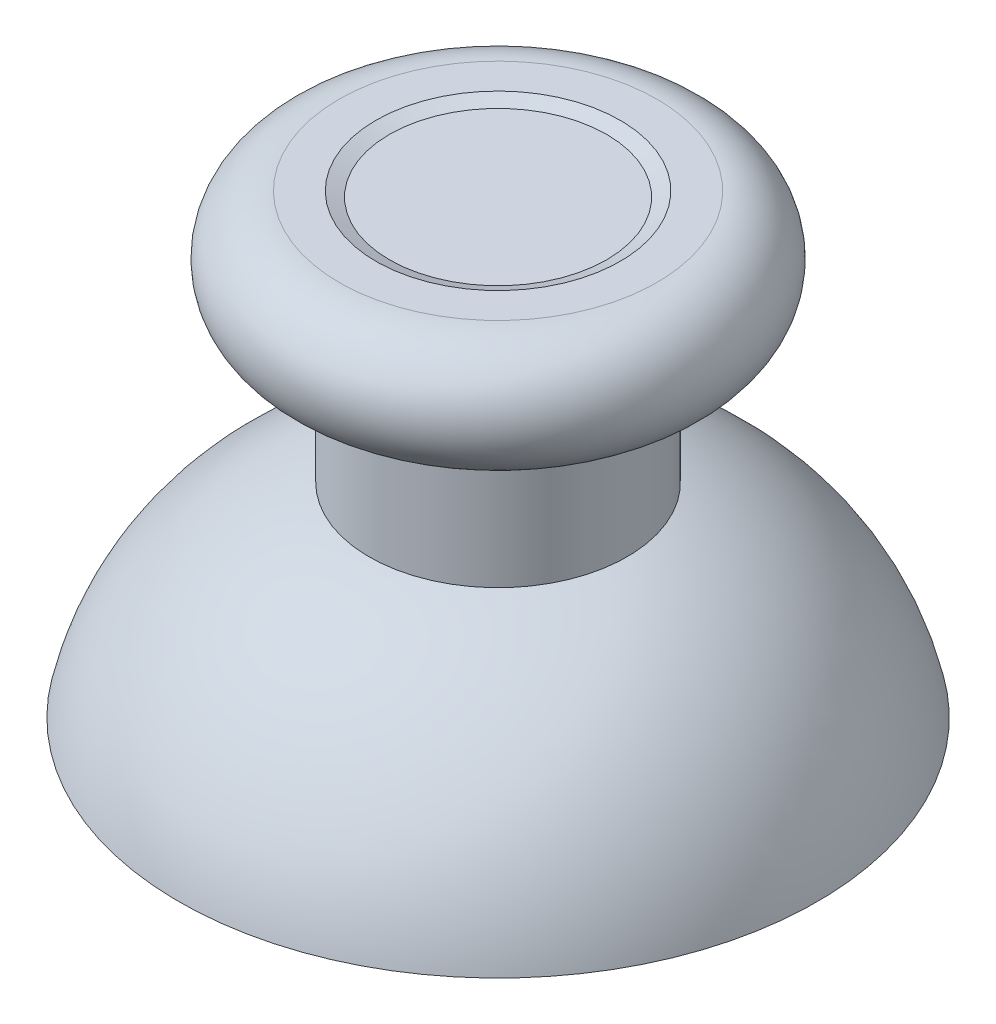
SolidWorks part; units mm, degrees
material "Rubber"
ref_plane "Front" through (0, 0, 0) normal (0, 0, 1) x (1, 0, 0)
ref_plane "Top" through (0, 0, 0) normal (0, 1, 0) x (1, 0, 0)
ref_plane "Right" through (0, 0, 0) normal (1, 0, 0) x (0, 0, -1)
sketch "Sketch1" plane through (0, 0, 0) normal (0, 0, 1) x (1, 0, 0)
  line L0 (0, 0) -> (11.75, 0)
  line L1 (0, 0) -> (0, -20.3128) construction
  line L2 (4.75, 7.5) -> (4.75, 12.5)
  line L3 (4.75, 12.5) -> (5.85, 12.5)
  line L4 (0, 0) -> (0, 16.8)
  line L5 (0, 16.8) -> (5.85, 16.8)
  line L6 (4.5, 16.8) -> (4, 16.6)
  line L7 (4, 16.6) -> (0, 16.6)
  line L8 (0, 6.5) -> (2, 6.5)
  arc A0 (4.75, 7.5) -> (11.75, 0) centre (1.9745, -2.1071) cw
  arc A1 (5.85, 12.5) -> (5.85, 16.8) centre (5.85, 14.65) ccw
  arc A2 (10.1492, 0) -> (2, 6.5) centre (2, -1.8584) ccw
  point P19 (10.3541, 0)
  point P20 (0, 0)
  dimension "D5" = 16
  dimension "D7" = 10
  dimension "D11" = 0.25
  dimension "D1" = 23.5
  dimension "D2" = 9.5
  dimension "D3" = 5
  dimension "D4" = 4.3
  dimension "D6" = 7.5
  dimension "D8" = 0.2
  dimension "D9" = 4
  dimension "D10" = 4.5
  dimension "D12" = 6.5
  dimension "D13" = 2
revolve "Revolve1" add sketch "Sketch1" angle 360 about L1 region at (4.1618, 10.5801, 0)
sketch "Sketch2" plane through (0, 6.5, 0) normal (0, -1, 0) x (1, 0, 0)
  line L0 (0, 0.5) -> (0, -0.5) construction
  line L1 (1.5, 0.5) -> (1.5, -0.5)
  line L2 (-1.5, 0.5) -> (-1.5, -0.5)
  circle A0 centre (0, 0) radius 2.5
  arc A1 (1.5, 0.5) -> (-1.5, 0.5) centre (0, 0.5) ccw
  arc A2 (-1.5, -0.5) -> (1.5, -0.5) centre (0, -0.5) ccw
  circle A3 centre (0, 0) radius 0.5
  point P5 (0, 0)
  circle M1 centre (0, 0) radius 2
  dimension "D1" = 5
  dimension "D3" = 4
  dimension "D4" = 1
  dimension "D2" = 3
extrude "Boss-Extrude2" add sketch "Sketch2" along normal blind 4 contours A0 M1 | L2 A2 L1 A1 A3 | L0 A3 | A2 L2 A1 M1 | A3 L0 | A2 A1 L1 M1 region at (0.2122, 6.5, 0) region at (-0.2122, 6.5, 0) region at (1.5681, 6.5, 0) region at (1.45, 6.5, 0) region at (-1.5681, 6.5, 0) region at (-2.4293, 6.5, 0)
extrude "Cut-Extrude1" cut sketch "Sketch2<3>" along normal through all contours L2 A2 L1 A1 A3 | A3 region at (1.45, 6.5, 0)
sketch "Sketch2<3>" plane through (0, 6.5, 0) normal (0, -1, 0) x (1, 0, 0) same geometry as "Sketch2"
